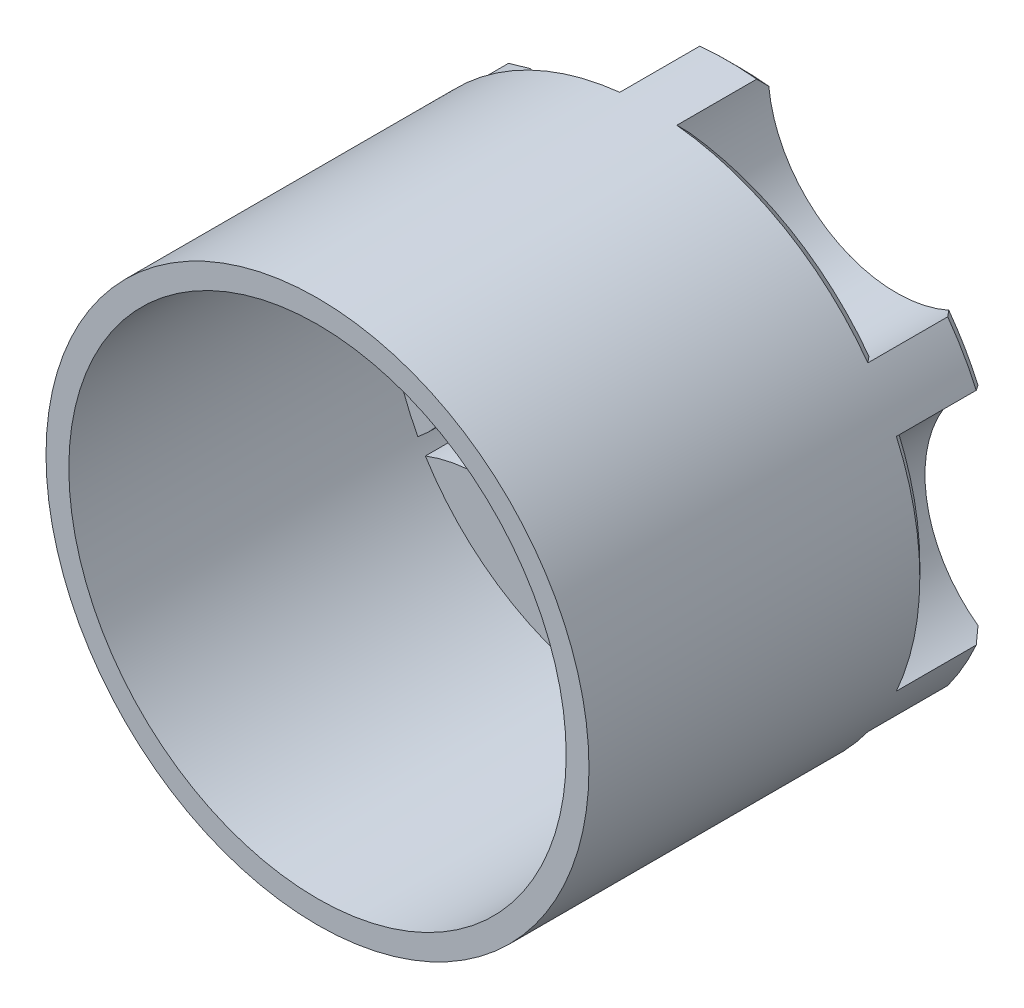
SolidWorks part; units mm, degrees
ref_plane "Front Plane" through (0, 0, 0) normal (0, 0, 1) x (1, 0, 0)
ref_plane "Top Plane" through (0, 0, 0) normal (0, 1, 0) x (1, 0, 0)
ref_plane "Right Plane" through (0, 0, 0) normal (1, 0, 0) x (0, 0, -1)
sketch "Sketch1" plane through (0, 0, 0) normal (0, 0, 1) x (1, 0, 0)
  line L0 (-1.4524, 0) -> (71.008, 0) construction
  line L1 (0, 0) -> (0, 72.303) construction
  circle A1 centre (0, 0) radius 23.8
  circle A2 centre (0, 0) radius 21.8
  arc A3 (21.7478, 9.6682) -> (21.7478, -9.6682) centre (27.5, 0) ccw
  arc A4 (19.1987, 10.3272) -> (19.1987, -10.3272) centre (27.5, 0) ccw
  circle A5 centre (27.5, 0) radius 13.25 construction
  circle A6 centre (27.5, 0) radius 11.25 construction
  arc A7 (18.5429, -11.463) -> (0.6557, -21.7901) centre (13.75, -23.8157) ccw
  arc A8 (19.2468, -14) -> (2.501, -23.6682) centre (13.75, -23.8157) ccw
  arc A9 (-0.6557, -21.7901) -> (-18.5429, -11.463) centre (-13.75, -23.8157) ccw
  arc A10 (-2.501, -23.6682) -> (-19.2468, -14) centre (-13.75, -23.8157) ccw
  arc A11 (-19.1987, -10.3272) -> (-19.1987, 10.3272) centre (-27.5, 0) ccw
  arc A12 (-21.7478, -9.6682) -> (-21.7478, 9.6682) centre (-27.5, 0) ccw
  arc A13 (-18.5429, 11.463) -> (-0.6557, 21.7901) centre (-13.75, 23.8157) ccw
  arc A14 (-19.2468, 14) -> (-2.501, 23.6682) centre (-13.75, 23.8157) ccw
  arc A15 (0.6557, 21.7901) -> (18.5429, 11.463) centre (13.75, 23.8157) ccw
  arc A16 (2.501, 23.6682) -> (19.2468, 14) centre (13.75, 23.8157) ccw
  arc A17 (16.724, 17.2136) -> (6.5455, 23.0902) centre (0, 0) ccw construction
  point P50 (0, 0)
  dimension "D2" = 22.5
  dimension "D6" = 0.2
  dimension "D1" = 2
  dimension "D3" = 27.5
  dimension "D4" = 2
  dimension "D5" = 6
extrude "Boss-Extrude1" add sketch "Sketch1" along normal blind 3 and the other way blind 27 contours A1 A14 A2 | A1 A16 A2 | A16 A1 A14 A2 | A16 A2 A3 A1 | A1 A3 A2 | A1 A8 A2 | A8 A1 A3 A2 | A10 A1 A8 A2 | A2 A10 A1 | A12 A1 A10 A2 | A2 A12 A1 | A14 A1 A12 A2 region at (22.1865, 0, 0) region at (19.691, 11.3686, 0) region at (19.691, -11.3686, 0) region at (11.0932, 19.214, 0) region at (11.0932, -19.214, 0) region at (0, 22.7372, 0) region at (0, -22.7372, 0) region at (-11.0932, 19.214, 0) region at (-11.0932, -19.214, 0) region at (-19.691, 11.3686, 0) region at (-19.691, -11.3686, 0) region at (-22.1865, 0, 0)
extrude "Boss-Extrude2" add sketch "Sketch1<5>" along normal blind 2 from surface contours A2 A16 | A2 A14 | A2 A12 | A2 A10 | A2 A8 | A2 A3 | A14 A2 A13 | A16 A1 A14 A2 | A14 A1 A12 A2 | A12 A2 A11 | A12 A1 A10 A2 | A10 A2 A9 | A10 A1 A8 A2 | A8 A2 A7 | A8 A1 A3 A2 | A2 A4 A3 | A16 A2 A3 A1 | A16 A2 A15 region at (19.691, 11.3686, 0) region at (19.691, -11.3686, 0) region at (16.0354, 0, 0) region at (19.2066, 0, 0) region at (0, 22.7372, 0) region at (9.6033, 16.6334, 0) region at (17.8051, 12.2088, 0) region at (0, -22.7372, 0) region at (8.0194, -13.89, 0) region at (9.6033, -16.6334, 0) region at (-19.691, 11.3686, 0) region at (-9.6033, 16.6334, 0) region at (-1.6706, 21.5241, 0) region at (-19.691, -11.3686, 0) region at (-8.0194, -13.89, 0) region at (-9.6033, -16.6334, 0) region at (-19.2066, 0, 0) region at (-19.4726, 9.3138, 0) starting at face at (23.8, 0, -27)
sketch "Sketch1<5>" plane through (0, 0, 0) normal (0, 0, 1) x (1, 0, 0) same geometry as "Sketch1"
extrude "Boss-Extrude4" add sketch "Sketch1<7>" against normal blind 5 from surface contours A14 A2 A13 | A14 A1 A12 A2 | A12 A2 A11 | A12 A1 A10 A2 | A10 A2 A9 | A10 A1 A8 A2 | A8 A2 A7 | A8 A1 A3 A2 | A2 A4 A3 | A16 A2 A3 A1 | A16 A2 A15 | A16 A1 A14 A2 region at (19.691, 11.3686, 0) region at (19.691, -11.3686, 0) region at (16.0354, 0, 0) region at (0, 22.7372, 0) region at (17.8051, 12.2088, 0) region at (0, -22.7372, 0) region at (8.0194, -13.89, 0) region at (-19.691, 11.3686, 0) region at (-1.6706, 21.5241, 0) region at (-19.691, -11.3686, 0) region at (-8.0194, -13.89, 0) region at (-19.4726, 9.3138, 0) starting at face at (0, 0, -27)
sketch "Sketch1<7>" plane through (0, 0, 0) normal (0, 0, 1) x (1, 0, 0) same geometry as "Sketch1"
extrude "Boss-Extrude5" add sketch "Sketch1<8>" against normal blind 2 from surface contours A14 A2 A13 | A16 A1 A14 A2 | A16 A2 A15 | A15 A2 A13 A11 A9 A7 A4 | A2 A4 A3 | A16 A2 A3 A1 | A8 A1 A3 A2 | A8 A2 A7 | A10 A1 A8 A2 | A10 A2 A9 | A12 A1 A10 A2 | A12 A2 A11 | A14 A1 A12 A2 region at (19.691, 11.3686, 0) region at (19.691, -11.3686, 0) region at (16.0354, 0, 0) region at (0, 22.7372, 0) region at (17.8051, 12.2088, 0) region at (0, 0, 0) region at (0, -22.7372, 0) region at (8.0194, -13.89, 0) region at (-19.691, 11.3686, 0) region at (-1.6706, 21.5241, 0) region at (-19.691, -11.3686, 0) region at (-8.0194, -13.89, 0) region at (-19.4726, 9.3138, 0) starting at face at (0, 0, -32)
sketch "Sketch1<8>" plane through (0, 0, 0) normal (0, 0, 1) x (1, 0, 0) same geometry as "Sketch1"
chamfer "Chamfer1" distance 1 angle 45 12 edges at (-20.6114, 11.9, -34) (-20.6114, -11.9, -34) (0, -23.8, -34) (20.6114, -11.9, -34) (20.6114, 11.9, -34) (0, 23.8, -34) (23.8, 0, -27) (11.9, -20.6114, -27) (-11.9, -20.6114, -27) (-23.8, 0, -27) (-11.9, 20.6114, -27) (11.9, 20.6114, -27)
